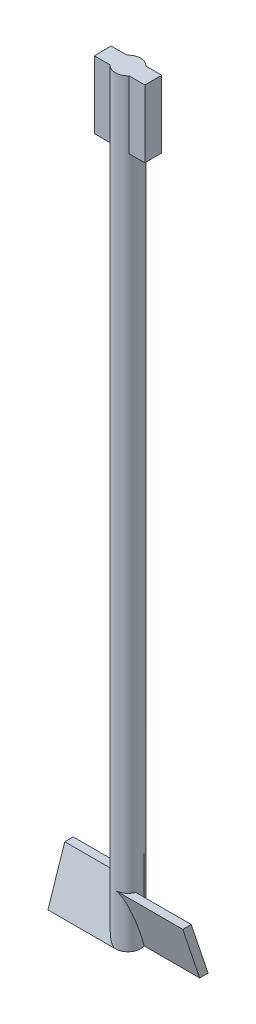
SolidWorks part; units mm, degrees
ref_plane "Front Plane" through (0, 0, 0) normal (0, 0, 1) x (1, 0, 0)
ref_plane "Top Plane" through (0, 0, 0) normal (0, 1, 0) x (1, 0, 0)
ref_plane "Right Plane" through (0, 0, 0) normal (1, 0, 0) x (0, 0, -1)
sketch "Sketch1" plane through (0, 0, 0) normal (0, 1, 0) x (1, 0, 0)
  circle A0 centre (0, 0) radius 1.5
  dimension "D1" = 3
extrude "Boss-Extrude1" add sketch "Sketch1" along normal blind 90
sketch "Sketch2" plane through (0, 90, 0) normal (0, 1, 0) x (1, 0, 0)
  line L1 (-3, 1) -> (3, 1)
  line L2 (-3, 1) -> (-3, -1)
  line L3 (-3, -1) -> (3, -1)
  line L4 (3, 1) -> (3, -1)
  line L5 (-3, 1) -> (3, -1) construction
  line L6 (-3, -1) -> (3, 1) construction
  point P0 (0, 0)
  dimension "D1" = 2
  dimension "D2" = 6
extrude "Boss-Extrude2" add sketch "Sketch2" against normal blind 8
sketch "Sketch3" plane through (0, 0, 0) normal (1, 0, 0) x (0, 0, -1)
  line L0 (-1.5, 6) -> (-0.5, 6)
  line L1 (-1.5, 90) -> (-1.5, 0) construction
  line L2 (1.5, 0) -> (0.5, 0)
  line L3 (-1.5, 0) -> (1.5, 0) construction
  line L4 (-1.5, 6) -> (0.5, 0)
  line L5 (-0.5, 6) -> (1.5, 0)
  dimension "D1" = 1
  dimension "D2" = 1
  dimension "D3" = 6
extrude "Boss-Extrude3" add sketch "Sketch3" along normal blind 8
sketch "Sketch4" plane through (0, 0, 0) normal (1, 0, 0) x (0, 0, -1)
  line L0 (1.5, 6) -> (0.5, 6)
  line L2 (1.5, 0) -> (1.5, 90) construction
  line L3 (-1.5, 0) -> (1.5, 0) construction
  line L4 (-1.5, 0) -> (-0.5, 0)
  line L5 (1.5, 6) -> (-0.5, 0)
  line L6 (0.5, 6) -> (-1.5, 0)
  dimension "D1" = 1
  dimension "D2" = 6
  dimension "D3" = 1
extrude "Boss-Extrude4" add sketch "Sketch4" against normal blind 8
